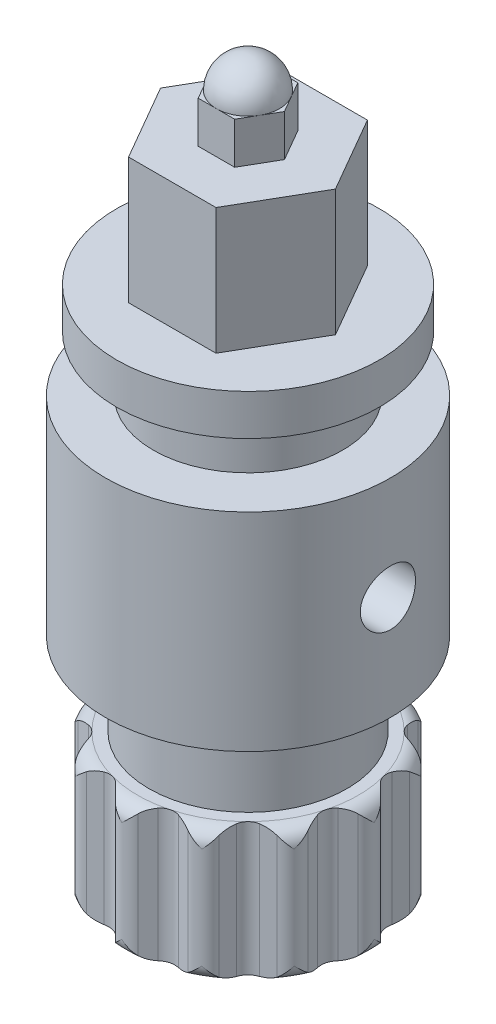
SolidWorks part; units mm, degrees
note: '?' marks a value the reader was unsure of.
material "AISI 316 Annealed Stainless Steel Bar (SS)"
ref_plane "Front Plane" through (0, 0, 0) normal (0, 0, 1) x (1, 0, 0)
ref_plane "Top Plane" through (0, 0, 0) normal (0, 1, 0) x (1, 0, 0)
ref_plane "Right Plane" through (0, 0, 0) normal (1, 0, 0) x (0, 0, -1)
ref_axis "CENTER" through (0, -35.7615, 0) along (0, 1, 0)?
sketch "Sketch1" plane through (0, 0, 0) normal (1, 0, 0) x (0, 0, -1)
  line L0 (0, 12.9986) -> (0, -68783.2739) construction
  line L1 (-6.35, 110.4018) -> (-6.35, 102.0198)
  line L2 (-6.35, 102.0198) -> (-15.24, 102.0198)
  line L3 (-15.24, 102.0198) -> (-15.24, 76.6198)
  line L4 (-15.24, 76.6198) -> (-26.416, 76.6198)
  line L5 (-26.416, 76.6198) -> (-26.416, 68.3953)
  line L6 (-26.416, 68.3953) -> (-19.05, 68.3953)
  line L7 (-19.05, 68.3953) -> (-19.05, 57.2193)
  line L8 (-19.05, 57.2193) -> (-28.702, 57.2193)
  line L9 (-28.702, 57.2193) -> (-28.702, 15.4617)
  line L10 (-28.702, 15.4617) -> (-19.939, 15.4617)
  line L11 (-19.939, 15.4617) -> (-19.939, -1.3263)
  line L12 (-19.939, -1.3263) -> (-22.225, -1.3263)
  line L13 (-25.4, -4.5013) -> (-25.4, -24.8532)
  line L14 (-22.225, -28.0282) -> (0, -28.0282)
  line L15 (0, -28.0282) -> (0, 116.7518)
  arc A0 (0, 116.7518) -> (-6.35, 110.4018) centre (0, 110.4018) ccw
  arc A1 (-22.225, -1.3263) -> (-25.4, -4.5013) centre (-22.225, -4.5013) ccw
  arc A2 (-25.4, -24.8532) -> (-22.225, -28.0282) centre (-22.225, -24.8532) ccw
  dimension "D13" = 3.175
  dimension "D1" = 12.7
  dimension "D2" = 30.48
  dimension "D3" = 52.832
  dimension "D4" = 38.1
  dimension "D5" = 57.404
  dimension "D6" = 39.878
  dimension "D7" = 50.8
  dimension "D8" = 14.732
  dimension "D9" = 25.4
  dimension "D10" = 11.176
  dimension "D11" = 41.7576
  dimension "D12" = 144.78
revolve "BASE" add sketch "Sketch1" angle 360 about L0
ref_point "HEX_REF"
sketch "Sketch2" plane through (0, 102.0198, 0) normal (0, 1, 0) x (1, 0, 0)
  line L1 (3.6662, 6.35) -> (-3.6662, 6.35)
  line L2 (-3.6662, 6.35) -> (-7.3323, 0)
  line L3 (-7.3323, 0) -> (-3.6662, -6.35)
  line L4 (-3.6662, -6.35) -> (3.6662, -6.35)
  line L5 (3.6662, -6.35) -> (7.3323, 0)
  line L6 (7.3323, 0) -> (3.6662, 6.35)
  circle A0 centre (0, 0) radius 6.35 construction
  circle A1 centre (0, 0) radius 6.35 construction
  point P1 (0, 0)
extrude "TOP_HEX" add sketch "Sketch2" along normal up to vertex (8.382 mm away)
sketch "Sketch3" plane through (0, 76.6198, 0) normal (0, 1, 0) x (1, 0, 0)
  line L1 (17.5976, 0) -> (8.7988, 15.24)
  line L2 (8.7988, 15.24) -> (-8.7988, 15.24)
  line L3 (-8.7988, 15.24) -> (-17.5976, 0)
  line L4 (-17.5976, 0) -> (-8.7988, -15.24)
  line L5 (-8.7988, -15.24) -> (8.7988, -15.24)
  line L6 (8.7988, -15.24) -> (17.5976, 0)
  circle A0 centre (0, 0) radius 15.24 construction
  circle A1 centre (0, 0) radius 15.24 construction
  point P1 (0, 0)
extrude "MAIN_HEX" add sketch "Sketch3" along normal up to surface (25.4 mm away) up to face at (0, 102.0198, 15.24)
sketch "Sketch4" plane through (0, -28.0282, 0) normal (0, -1, 0) x (1, 0, 0)
  line L0 (0, 0) -> (0, 25.4) construction
  line L1 (0, 0) -> (6.574, 24.5345) construction
  line L2 (2.2966, 24.4173) -> (4.2774, 22.3423)
  line L3 (0, 0) -> (3.5226, 26.7566) construction
  line L4 (2.8726, 21.8194) -> (49575.1156, -6504.4902) construction
  line L5 (3.287, 24.9673) -> (49575.5301, -6501.3424) construction
  line L6 (10.2197, 22.2943) -> (7.4668, 21.4876)
  line L7 (0, 25.4) -> (0, 26.9875)
  line L8 (12.7, 21.997) -> (13.4938, 23.3719)
  arc A0 (2.2966, 24.4173) -> (0, 25.4) centre (0, 22.225) ccw
  circle A1 centre (0, 0) radius 25.4 construction
  arc A2 (4.2774, 22.3423) -> (7.4668, 21.4876) centre (6.574, 24.5345) ccw
  arc A3 (6.9849, 26.0679) -> (0, 26.9875) centre (0, 0) ccw construction
  arc A4 (10.2197, 22.2943) -> (12.7, 21.997) centre (11.1125, 19.2474) cw
  arc A5 (13.4938, 23.3719) -> (0, 26.9875) centre (0, 0) ccw
  point P22 (0, 0)
  dimension "D1" = 6.35
  dimension "D2" = 15
  dimension "D3" = 1.5875
  dimension "D4" = 3.175
extrude "HANDLE_CUT" cut sketch "Sketch4" against normal up to surface (26.7019 mm away) up to face at (0, -1.3263, 22.225)
pattern_circular "HANDLE" count 12 over 360 about axis through (0, 0, 0) along (0, 1, 0) of "HANDLE_CUT"
sketch "Sketch5" plane through (0, 0, 0) normal (1, 0, 0) x (0, 0, -1)
  line L0 (0, 57.2193) -> (0, 15.4617) construction
  line L1 (28.702, 57.2193) -> (-28.702, 57.2193) construction
  line L2 (-28.702, 15.4617) -> (28.702, 15.4617) construction
  circle A0 centre (0, 36.3405) radius 5.5563
  dimension "D1" = 11.1125
extrude "NPTF_HOLE" cut sketch "Sketch5" against normal through all both and the other way through all
